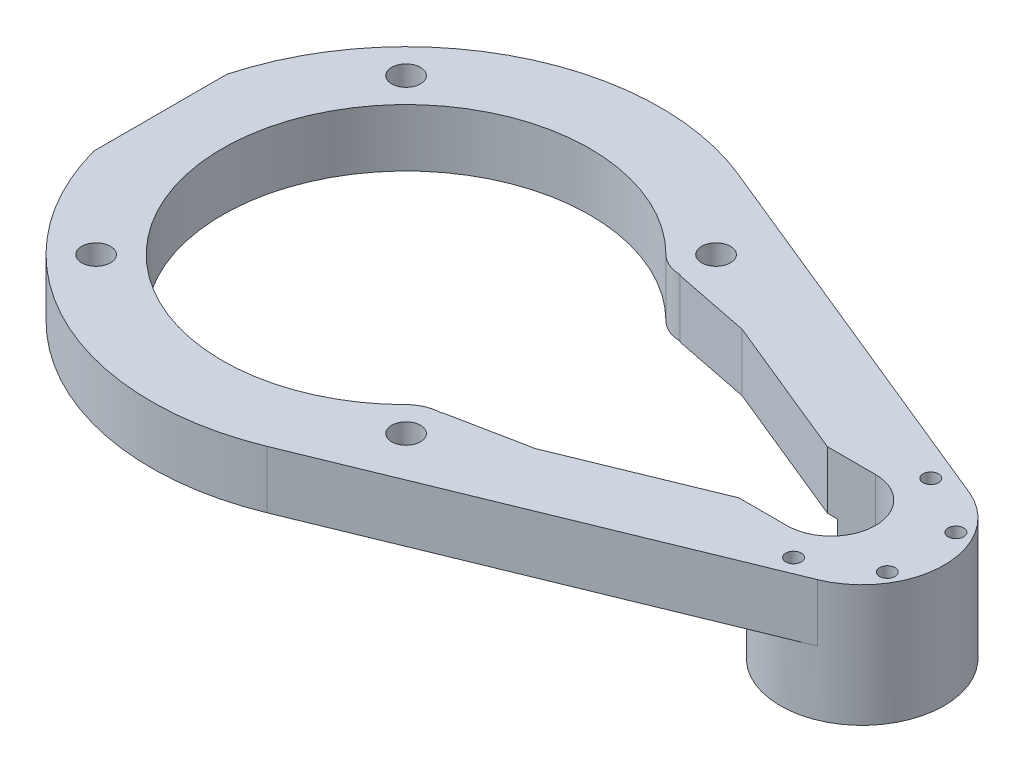
SolidWorks part; units mm, degrees
ref_plane "Front Plane" through (0, 0, 0) normal (0, 0, 1) x (1, 0, 0)
ref_plane "Top Plane" through (0, 0, 0) normal (0, 1, 0) x (1, 0, 0)
ref_plane "Right Plane" through (0, 0, 0) normal (1, 0, 0) x (0, 0, -1)
sketch "Sketch1" plane through (0, 0, 0) normal (0, 1, 0) x (1, 0, 0)
  line L0 (-75.4693, 0) -> (91.4794, 0) construction
  line L1 (35, 35) -> (-35, 35)
  line L2 (35, 35) -> (35, -35)
  line L3 (35, -35) -> (-35, -35)
  line L4 (-35, 35) -> (-35, -35)
  line L5 (35, 35) -> (-35, -35) construction
  line L6 (35, -35) -> (-35, 35) construction
  line L7 (110.0044, 17.1227) -> (21.7695, 53.217)
  line L8 (110.0044, -17.1227) -> (21.7695, -53.217)
  line L9 (86.9809, 9.254) -> (52.5473, 23.3398)
  line L10 (86.9809, -9.254) -> (52.5473, -23.3398)
  line L11 (52.5473, 23.3398) -> (33.4341, 27.1547)
  line L12 (52.5473, -23.3398) -> (33.4341, -27.1547)
  line L13 (-55.5, 15.0236) -> (-55.5, -15.0236)
  line L14 (96, 10) -> (85.1573, 10)
  line L15 (96, -10) -> (85.1573, -10)
  circle A0 centre (-35, 35) radius 3.25
  circle A1 centre (35, 35) radius 3.25
  circle A2 centre (35, -35) radius 3.25
  circle A3 centre (-35, -35) radius 3.25
  circle A4 centre (-35, 35) radius 8
  circle A5 centre (35, 35) radius 8
  circle A6 centre (35, -35) radius 8
  circle A7 centre (-35, -35) radius 8
  circle A8 centre (0, 0) radius 57.4975
  circle A9 centre (0, 0) radius 41.4975
  circle A10 centre (103, 0) radius 18.5
  circle A11 centre (96, 0) radius 10
  point P0 (0, 0)
  dimension "D2" = 6.5
  dimension "D3" = 16
  dimension "D4" = 37
  dimension "D8" = 20
  dimension "D1" = 70
  dimension "D5" = 96
  dimension "D6" = 16
  dimension "D7" = 55.5
  dimension "D9" = 7
extrude "Boss-Extrude1" add sketch "Sketch1" along normal blind 13 contours A9 L1 A5 A8 A4 | L1 A4 L4 A0 | L4 A4 L1 A0 | A9 L1 A4 | A9 L4 A4 A8 A7 | A9 A4 L4 | A9 L4 A7 | A9 A7 L3 | L3 A7 L4 A3 | A9 L3 A7 A8 A6 | L4 A7 L3 A3 | L2 A6 L3 A2 | L3 A6 L2 A2 | A9 L3 A6 | A9 A5 L1 | L1 A5 L2 A1 | L2 A5 L1 A1 | A10 L7 A8 L9 | A10 L10 A8 L8 | A10 | L11 A8 A5 L2 | A6 A8 L12 L2 region at (-31.2062, 0, -31.2062) region at (0, 0, -46.6413) region at (-29.375, 0, -35.2263) region at (-25.7994, 0, -33.5313) region at (-46.2472, 0, 0) region at (-33.5313, 0, -25.7994) region at (25.7994, 0, -33.5313) region at (68.8956, 0, -26.4915) region at (32.0251, 0, -42.182) region at (31.2062, 0, -31.2062) region at (107.2884, 0, 0) region at (45.0485, 0, -28.9885) region at (-33.5313, 0, 25.7994) region at (-42.182, 0, 32.0251) region at (0, 0, 46.6413) region at (-31.2062, 0, 31.2062) region at (-25.7994, 0, 33.5313) region at (68.8956, 0, 26.4915) region at (45.0485, 0, 28.9885) region at (31.2062, 0, 31.2062) region at (25.7994, 0, 33.5313) region at (32.0251, 0, 42.182)
sketch "Sketch2" plane through (0, 0, 0) normal (0, 1, 0) x (1, 0, 0)
  line L0 (96, -10) -> (85.1573, -10) construction
  line L1 (96, 10) -> (85.1573, 10) construction
  line L2 (96, -10) -> (85.1573, -10)
  line L3 (96, 10) -> (85.1573, 10)
  circle A0 centre (103, 0) radius 18.5
  arc A1 (110.0044, -17.1227) -> (110.0044, 17.1227) centre (103, 0) ccw construction
  arc A2 (96, -10) -> (96, 10) centre (96, 0) ccw construction
  arc A3 (96, -10) -> (96, 10) centre (96, 0) ccw
extrude "Boss-Extrude2" add sketch "Sketch2" against normal blind 14.5 contours A0 L3 region at (107.2884, 0, 0)
sketch "Sketch3" plane through (0, -14.5, 0) normal (0, -1, 0) x (1, 0, 0)
  line L0 (103, 18.5) -> (103, -18.5) construction
  line L1 (103, 0) -> (121.5, 0) construction
  line L2 (103, 0) -> (116.4234, 7.75) construction
  line L3 (103, 0) -> (103, 15.5) construction
  arc A0 (87.4356, -10) -> (87.4356, 10) centre (103, 0) ccw construction
  arc A1 (110.0044, 17.1227) -> (87.4356, 10) centre (103, 0) ccw construction
  circle A2 centre (103, 15.5) radius 1.75
  circle A3 centre (116.4234, 7.75) radius 1.75
  circle A4 centre (116.4234, -7.75) radius 1.75
  circle A5 centre (103, -15.5) radius 1.75
  circle A6 centre (89.5766, -7.75) radius 1.75 [skipped]
  circle A7 centre (89.5766, 7.75) radius 1.75 [skipped]
  point P11 (103, 0)
  point P27 (103, 0)
  dimension "D1" = 3.5
  dimension "D2" = 15.5
  dimension "D3" = 6
extrude "Cut-Extrude1" cut sketch "Sketch3" against normal up to next
sketch "Sketch4" plane through (0, 0, 0) normal (0, -1, 0) x (1, 0, 0)
  line L0 (-38.7123, 38.7123) -> (-35, 35) construction
  line L1 (-29.1444, 33.431) -> (-30.7134, 39.2866)
  line L2 (-30.7134, 39.2866) -> (-36.569, 40.8556)
  line L3 (-36.569, 40.8556) -> (-40.8556, 36.569)
  line L4 (-40.8556, 36.569) -> (-39.2866, 30.7134)
  line L5 (-39.2866, 30.7134) -> (-33.431, 29.1444)
  line L6 (-33.431, 29.1444) -> (-29.1444, 33.431)
  line L7 (36.569, 40.8556) -> (30.7134, 39.2866)
  line L8 (40.8556, 36.569) -> (36.569, 40.8556)
  line L9 (39.2866, 30.7134) -> (40.8556, 36.569)
  line L10 (33.431, 29.1444) -> (39.2866, 30.7134)
  line L11 (29.1444, 33.431) -> (33.431, 29.1444)
  line L12 (30.7134, 39.2866) -> (29.1444, 33.431)
  line L13 (40.8556, -36.569) -> (39.2866, -30.7134)
  line L14 (36.569, -40.8556) -> (40.8556, -36.569)
  line L15 (30.7134, -39.2866) -> (36.569, -40.8556)
  line L16 (29.1444, -33.431) -> (30.7134, -39.2866)
  line L17 (33.431, -29.1444) -> (29.1444, -33.431)
  line L18 (39.2866, -30.7134) -> (33.431, -29.1444)
  line L19 (-36.569, -40.8556) -> (-30.7134, -39.2866)
  line L20 (-40.8556, -36.569) -> (-36.569, -40.8556)
  line L21 (-39.2866, -30.7134) -> (-40.8556, -36.569)
  line L22 (-33.431, -29.1444) -> (-39.2866, -30.7134)
  line L23 (-29.1444, -33.431) -> (-33.431, -29.1444)
  line L24 (-30.7134, -39.2866) -> (-29.1444, -33.431)
  line L25 (0, 13.683) -> (0, -11.8209) construction
  circle A0 centre (0, 0) radius 49.4975
  circle A1 centre (-35, 35) radius 5.25 construction
  point P15 (0, 0)
  point P34 (0, 0)
  circle M27 centre (35, 35) radius 3.25
  circle M28 centre (-35, 35) radius 3.25
  circle M47 centre (-35, -35) radius 3.25
  circle M48 centre (35, -35) radius 3.25
  dimension "D1" = 10.5
  dimension "D2" = 4
extrude "Cut-Extrude2" cut sketch "Sketch4" against normal blind 5 contours L1 A0 L5 L6 M28 | A0 L1 L2 L3 L4 L5 M28 | L10 A0 L12 L11 M27 | A0 L10 L9 L8 L7 L12 M27 | L16 A0 L18 L17 M48 | A0 L16 L15 L14 L13 L18 M48 | A0 L22 L21 L20 L19 L24 M47 | L22 A0 L24 L23 M47 region at (-31.3852, 0, 31.3852) region at (-31.7222, 0, 38.1846) region at (31.5415, 0, 37.9671) region at (30.8013, 0, 39.0549) region at (-38.1846, 0, -31.7222) region at (-36.1289, 0, -30.0101) region at (37.9671, 0, -31.5415) region at (39.0549, 0, -30.8013)
